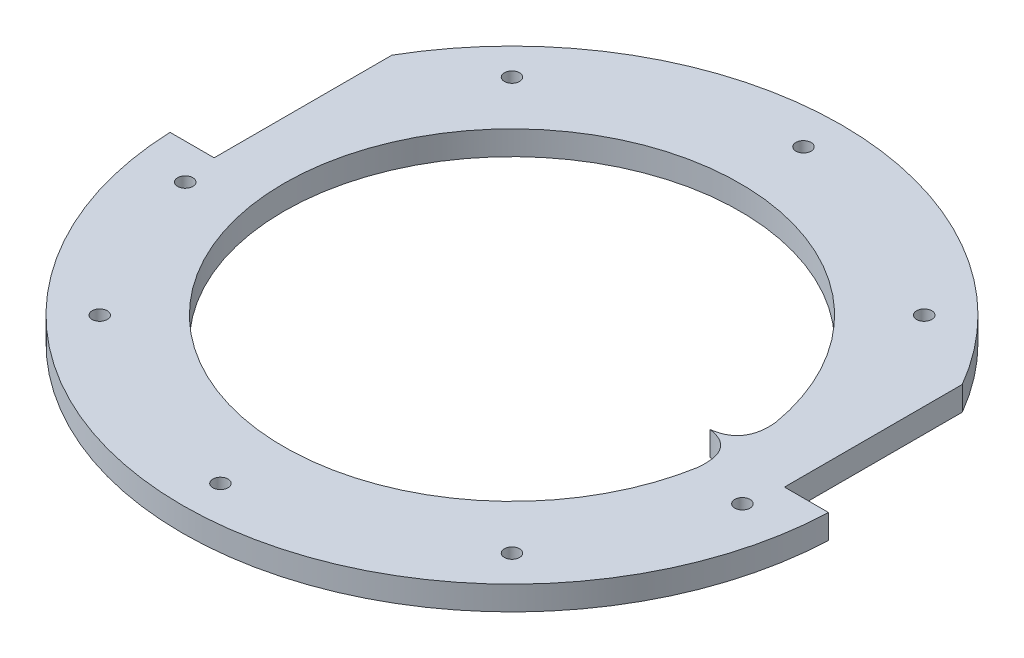
SolidWorks part; units mm, degrees
note: '?' marks a value the reader was unsure of.
ref_plane "Front Plane" through (0, 0, 0) normal (0, 0, 1) x (1, 0, 0)
ref_plane "Top Plane" through (0, 0, 0) normal (0, 1, 0) x (1, 0, 0)
ref_plane "Right Plane" through (0, 0, 0) normal (1, 0, 0) x (0, 0, -1)
sketch "Sketch1" plane through (0, 0, 0) normal (0, 1, 0) x (1, 0, 0)
  line L0 (0, -45) -> (0, 45) construction
  line L1 (-45, 0) -> (45, 0) construction
  line L2 (-40.6586, -40.6586) -> (40.6586, 40.6586) construction
  line L3 (-40.6586, 40.6586) -> (40.6586, -40.6586) construction
  line L4 (40.6586, -40.6586) -> (45.9619, -45.9619) construction
  line L6 (0, -65) -> (0, -57.5) construction
  line L7 (40.6586, 40.6586) -> (45.9619, 45.9619) construction
  line L9 (44.3498, 7.6221) -> (45, 0.795) construction
  line L10 (45, 0.795) -> (39.0888, 0) construction
  line L11 (44.3498, -7.6221) -> (45, -0.795) construction
  line L12 (45, -0.795) -> (39.0888, 0) construction
  arc A0 (44.3498, 7.6221) -> (44.3498, -7.6221) centre (0, 0) ccw
  circle A1 centre (0, 0) radius 65
  circle A2 centre (0, -57.5) radius 1.5
  circle A3 centre (40.6586, -40.6586) radius 1.5
  circle A5 centre (40.6586, 40.6586) radius 1.5
  circle A6 centre (0, 57.5) radius 1.5
  circle A8 centre (-40.6586, 40.6586) radius 1.5
  circle A9 centre (-40.6586, -40.6586) radius 1.5
  spline S0 degree 2 poles (44.3498, 7.6221) (45, 0.795) (39.0888, 0) knots 0 0 0 1 1 1
  spline S1 degree 2 poles (44.3498, -7.6221) (45, -0.795) (39.0888, 0) knots 0 0 0 1 1 1
  point P7 (0, 0)
  point P10 (0, 0)
  point P13 (0, 0)
  point P16 (0, 0)
extrude "Boss-Extrude1" add sketch "Sketch1" along normal blind 4.75
sketch "Sketch3" plane through (0, 4.75, 0) normal (0, 1, 0) x (1, 0, 0)
  line L0 (0, 45) -> (0, 0) construction
  line L1 (-65, 0) -> (-61.25, 0) construction
  line L2 (66.25, 2.5) -> (66.25, -2.5)
  line L3 (-66.25, 2.5) -> (-56.25, 2.5)
  line L4 (-66.25, 2.5) -> (-66.25, -2.5)
  line L5 (-66.25, -2.5) -> (-56.25, -2.5)
  line L6 (-56.25, 2.5) -> (-56.25, -2.5)
  line L7 (-66.25, 2.5) -> (-56.25, -2.5) construction
  line L8 (-66.25, -2.5) -> (-56.25, 2.5) construction
  line L9 (66.25, -2.5) -> (56.25, -2.5)
  line L10 (66.25, 2.5) -> (56.25, 2.5)
  line L11 (56.25, 2.5) -> (56.25, -2.5)
  circle A0 centre (0, 0) radius 65 construction
  arc A1 (44.3498, 7.6221) -> (44.3498, -7.6221) centre (0, 0) ccw construction
extrude "Cut-Extrude1" cut sketch "Sketch3" against normal blind 5
sketch "Sketch4" plane through (0, 4.75, 0) normal (0, 1, 0) x (1, 0, 0)
  line L1 (0, 45) -> (0, -45) construction
  line L2 (-45, 0) -> (39.0888, 0) construction
  line L3 (56.25, -2.5) -> (64.9519, -2.5) construction
  circle A0 centre (54.9519, -9.5) radius 1.5
  arc A1 (44.3498, 7.6221) -> (44.3498, -7.6221) centre (0, 0) ccw construction
  circle A2 centre (-54.9519, -9.5) radius 1.5
  dimension "D1" = 10
  dimension "D2" = 7
extrude "Cut-Extrude2" cut sketch "Sketch4" against normal through all contours A2 | A0
sketch "Sketch5" plane through (0, 4.75, 0) normal (0, 1, 0) x (1, 0, 0)
  line L0 (-56.25, 2.5) -> (-56.25, 32.572)
  line L1 (-56.25, 2.5) -> (-64.9519, 2.5) construction
  line L2 (-56.25, 2.5) -> (-64.9519, 2.5)
  line L3 (0, 45) -> (0, -45) construction
  line L4 (56.25, 2.5) -> (64.9519, 2.5)
  line L5 (56.25, 2.5) -> (56.25, 32.572)
  arc A0 (64.9519, 2.5) -> (-64.9519, 2.5) centre (0, 0) ccw construction
  arc A1 (64.9519, 2.5) -> (-64.9519, 2.5) centre (0, 0) ccw
  arc A2 (44.3498, 7.6221) -> (44.3498, -7.6221) centre (0, 0) ccw construction
  line M14 (56.25, 2.5) -> (64.9519, 2.5)
  arc M15 (64.9519, 2.5) -> (-64.9519, 2.5) centre (0, 0) ccw
  line M16 (-64.9519, 2.5) -> (-56.25, 2.5)
extrude "Cut-Extrude3" cut sketch "Sketch5" against normal through all contours L0 M16 M15 | L5 M14 M15
convert to sheet metal "Convert-Solid1" [suppressed] bend radius? 10 thickness? 4.75
sketch "Bend-Lines1" [suppressed] plane through (0, 0, 0) normal (0, 1, 0) x (1, 0, 0)
sketch "Bounding-Box1" [suppressed] plane through (0, 0, 0) normal (0, 1, 0) x (1, 0, 0)
sheet metal parameters "Sheet-Metal5" thickness 4.75 parameters "D1"=10
flat pattern "Flat-Pattern5" [suppressed]
sketch "Bend-Lines2" [suppressed] plane through (0, 0, 0) normal (0, 1, 0) x (1, 0, 0)
sketch3d "Bounding-Box2" [suppressed]
  line L0 (78.74, 47.4343, 0) -> (47.4343, -78.74, 0) construction
  line L1 (-44.9481, 78.1232, 0) -> (-76.2538, -48.0511, 0) construction
  line L2 (78.74, 47.4343, 0) -> (-44.9481, 78.1232, 0) construction
  line L3 (47.4343, -78.74, 0) -> (-76.2538, -48.0511, 0) construction
